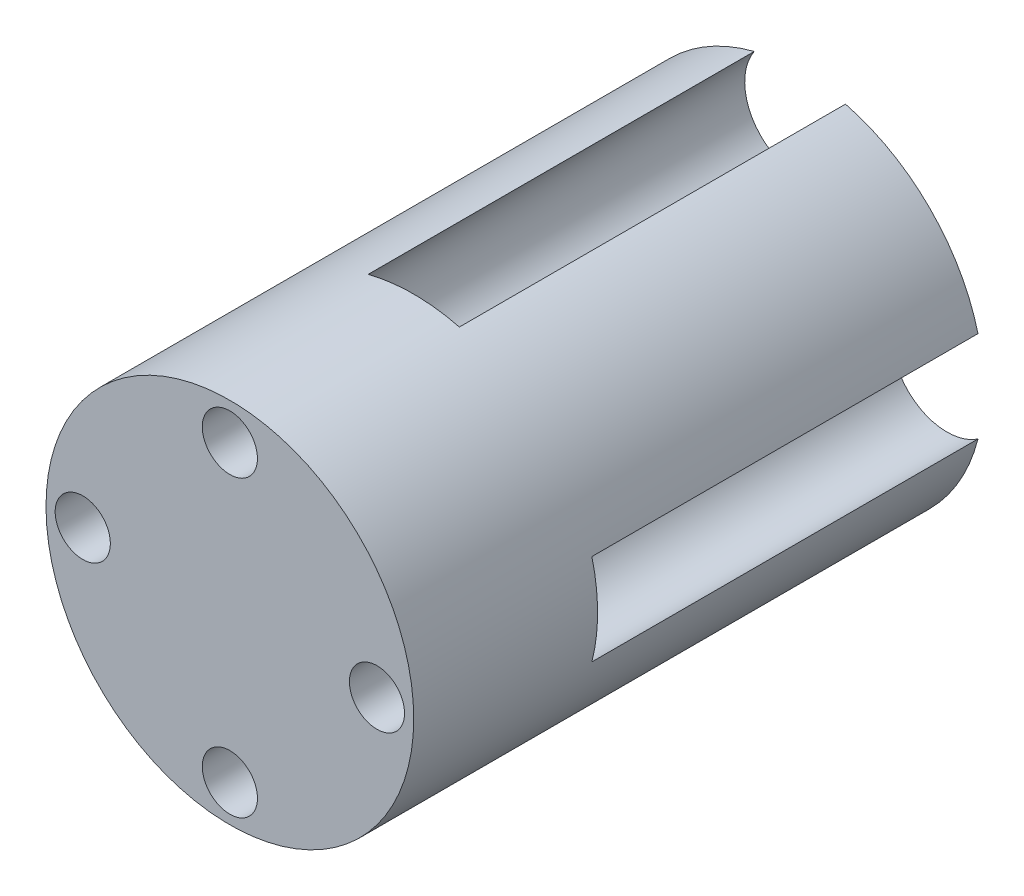
SolidWorks part; units mm, degrees
ref_plane "Ebene vorne" through (0, 0, 0) normal (0, 0, 1) x (1, 0, 0)
ref_plane "Ebene oben" through (0, 0, 0) normal (0, 1, 0) x (1, 0, 0)
ref_plane "Ebene rechts" through (0, 0, 0) normal (1, 0, 0) x (0, 0, -1)
sketch "Skizze1" plane through (0, 0, 0) normal (0, 0, 1) x (1, 0, 0)
  circle A0 centre (0, 0) radius 10
  circle A1 centre (0, 0) radius 8
  circle A2 centre (8, 0) radius 1.5
  circle A3 centre (0, 0) radius 9.5
  circle A4 centre (0, -8) radius 1.5
  circle A5 centre (-8, 0) radius 1.5
  circle A6 centre (0, 8) radius 1.5
  point P16 (0, 0)
  dimension "D1" = 20
  dimension "D2" = 19
  dimension "D3" = 3
  dimension "D4" = 4
extrude "Aufsatz-Linear austragen1" add sketch "Skizze1" along normal blind 31 contours A0 A3 | A6 A3 A5 A1 | A5 A3 A4 A1 | A4 A3 A2 A1 | A6 A1 A2 A3 | A6 A1 A5 A4 A2 region at (-9.7172, 0, 0) region at (0, 0, 0) region at (5.7904, 5.7904, 0) region at (5.7904, -5.7904, 0) region at (-5.7904, 5.7904, 0) region at (-5.7904, -5.7904, 0)
sketch "Skizze2" plane through (0, 0, 0) normal (0, 0, -1) x (-1, 0, 0)
  circle A0 centre (0, 8) radius 3
  circle A1 centre (8, 0) radius 3
  circle A2 centre (0, -8) radius 3
  circle A3 centre (-8, 0) radius 3
  point P12 (0, 0)
  dimension "D1" = 6
  dimension "D2" = 4
extrude "Schnitt-Linear austragen1" cut sketch "Skizze2" against normal offset from surface (21 mm away) 10 up to face at (9.5, 0, 31)
sketch "Skizze3" plane through (0, 0, 0) normal (0, 0, -1) x (-1, 0, 0)
  line L0 (0, 0) -> (-5.6569, 5.6569) construction
  circle A0 centre (0, 0) radius 8
  circle A1 centre (-5.6569, 5.6569) radius 1.25
  circle A2 centre (5.6569, 5.6569) radius 1.25
  circle A3 centre (5.6569, -5.6569) radius 1.25
  circle A4 centre (-5.6569, -5.6569) radius 1.25
  point P15 (0, 0)
  dimension "D1" = 4
extrude "Schnitt-Linear austragen2" cut sketch "Skizze3" against normal blind 16 contours A0 A1 | L0 A1 A0 | A1 L0 A0 | A0 A2 | A0 A2 | A0 A3 | A0 A3 | A0 A4 | A0 A4 region at (5.6348, 4.9043, 0) region at (4.9043, 5.6348, 0) region at (6.0193, 6.0193, 0) region at (5.2696, -5.2696, 0) region at (6.0193, -6.0193, 0) region at (-6.0193, 6.0193, 0) region at (-5.2696, 5.2696, 0) region at (-5.2696, -5.2696, 0) region at (-6.0193, -6.0193, 0)
